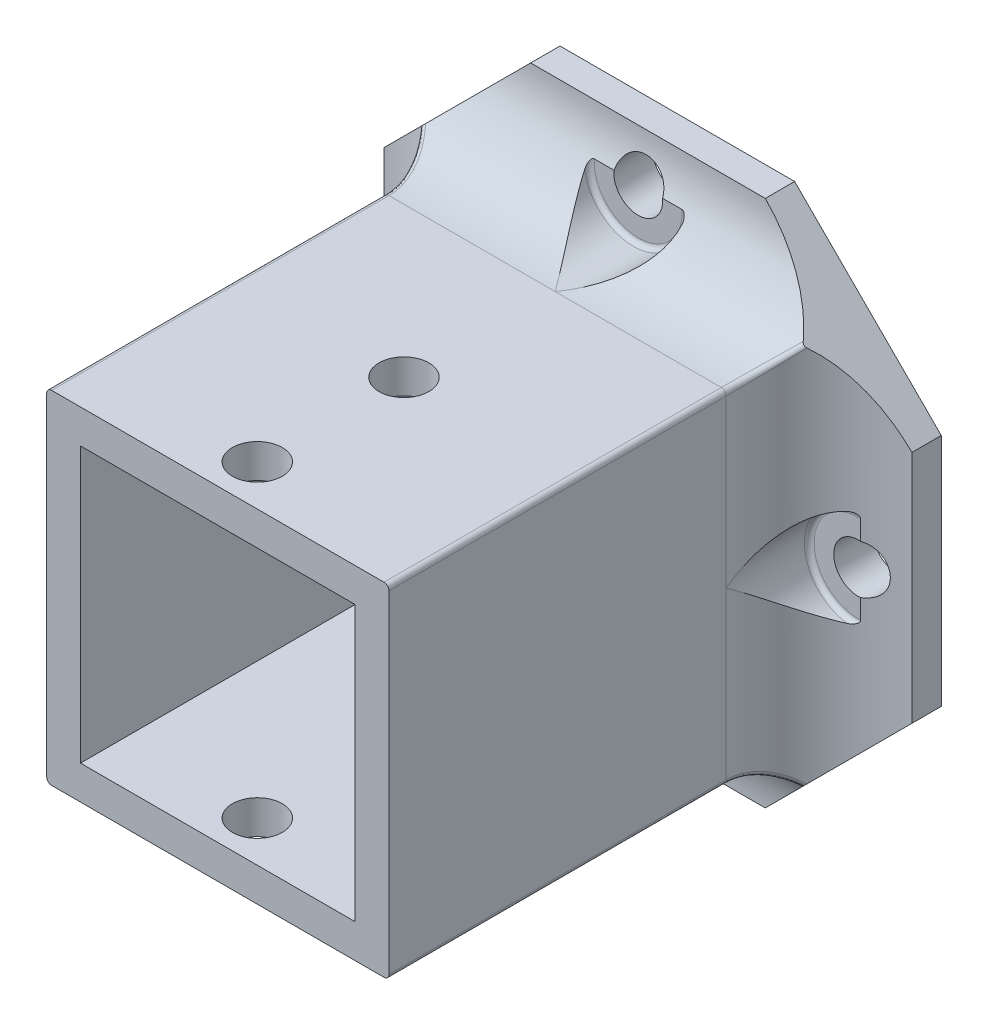
SolidWorks part; units mm, degrees
ref_plane "前视基准面" through (0, 0, 0) normal (0, 0, 1) x (1, 0, 0)
ref_plane "上视基准面" through (0, 0, 0) normal (0, 1, 0) x (1, 0, 0)
ref_plane "右视基准面" through (0, 0, 0) normal (1, 0, 0) x (0, 0, -1)
other "Configuration Table"
sketch "草图1" plane through (0, 0, 0) normal (0, 0, 1) x (1, 0, 0)
  line L1 (14.2, -14.2) -> (-14.2, -14.2)
  line L2 (14.2, -14.2) -> (14.2, 14.2)
  line L3 (14.2, 14.2) -> (-14.2, 14.2)
  line L4 (-14.2, -14.2) -> (-14.2, 14.2)
  line L5 (14.2, -14.2) -> (-14.2, 14.2) construction
  line L6 (14.2, 14.2) -> (-14.2, -14.2) construction
  point P0 (0, 0)
  dimension "D1" = 28.4
  dimension "D2" = 28.4
extrude "凸台-拉伸1" add sketch "草图1" along normal blind 3
sketch "草图2" plane through (0, 0, 3) normal (0, 0, 1) x (1, 0, 0)
  circle A0 centre (0, 0) radius 1
extrude "切除-拉伸1" cut sketch "草图2" against normal blind 3
sketch "草图5" plane through (0, 0, 0) normal (0, 0, -1) x (-1, 0, 0)
  circle A0 centre (0, 22.5) radius 2.5
  circle A1 centre (22.5, 0) radius 2.5
  circle A2 centre (-22.5, 0) radius 2.5
  circle A3 centre (0, -22.5) radius 2.5
sketch "草图6" plane through (0, 0, 3) normal (0, 0, 1) x (1, 0, 0)
  line L0 (12, 27) -> (27, 12)
  line L1 (27, -27) -> (-27, -27)
  line L2 (27, -27) -> (27, 27)
  line L3 (27, 27) -> (-27, 27)
  line L4 (-27, -27) -> (-27, 27)
  line L5 (27, -27) -> (-27, 27) construction
  line L6 (27, 27) -> (-27, -27) construction
  line L7 (27, -12) -> (12, -27)
  line L8 (-12, -27) -> (-27, -12)
  line L9 (-27, 12) -> (-12, 27)
  point P0 (0, 0)
  line M6 (-14.2, 14.2) -> (-14.2, -14.2)
  line M7 (-14.2, -14.2) -> (14.2, -14.2)
  line M8 (14.2, -14.2) -> (14.2, 14.2)
  line M9 (14.2, 14.2) -> (-14.2, 14.2)
  dimension "D1" = 4.5
  dimension "D2" = 15
  dimension "D3" = 15
  dimension "D4" = 15
  dimension "D5" = 15
  dimension "D6" = 15
  dimension "D7" = 15
  dimension "D8" = 15
  dimension "D9" = 15
extrude "凸台-拉伸3" add sketch "草图6" against normal blind 3 contours L9 L4 L8 L1 L7 L2 L0 L3 M6 M9 M8 M7 region at (18.96, 18.96, 3)
extrude "切除-拉伸2" cut sketch "草图5" against normal blind 3
sketch "草图7" plane through (0, 0, 3) normal (0, 0, 1) x (1, 0, 0)
  line L1 (17.5, -17.5) -> (-17.5, -17.5)
  line L3 (17.5, -17.5) -> (17.5, 17.5)
  line L4 (17.5, 17.5) -> (-17.5, 17.5)
  line L5 (-17.5, -17.5) -> (-17.5, 17.5)
  line L6 (17.5, -17.5) -> (-17.5, 17.5) construction
  line L15 (17.5, 17.5) -> (-17.5, -17.5) construction
  line L16 (14.05, -14.05) -> (-14.05, -14.05)
  line L21 (14.05, -14.05) -> (14.05, 14.05)
  line L22 (14.05, 14.05) -> (-14.05, 14.05)
  line L23 (-14.05, -14.05) -> (-14.05, 14.05)
  line L24 (14.05, -14.05) -> (-14.05, 14.05) construction
  line L25 (14.05, 14.05) -> (-14.05, -14.05) construction
  point P0 (0, 0)
  point P7 (0, 0)
  dimension "D1" = 28.1
  dimension "D2" = 28.1
  dimension "D3" = 35
  dimension "D4" = 35
extrude "凸台-拉伸4" add sketch "草图7" along normal blind 73 contours L5 L1 L3 L4 L16 L23 L22 L21 region at (0, -17.005, 3)
sketch "草图8" plane through (-17.5, 0, 0) normal (-1, 0, 0) x (0, 0, 1)
  line L0 (67, 17.5) -> (67, -17.5)
  line L4 (67, 17.5) -> (76, 17.5)
  line L5 (67, 17.5) -> (67, -17.5)
  line L6 (67, -17.5) -> (76, -17.5)
  line L7 (76, 17.5) -> (76, -17.5)
  dimension "D1" = 9
sketch "草图9" plane through (0, -17.5, 0) normal (0, -1, 0) x (1, 0, 0)
  line L2 (17.5, 76) -> (-17.5, 76) construction
  circle A0 centre (-0.1414, 42.82) radius 2.55
  circle A1 centre (-0.1414, 27.82) radius 2.55
  dimension "D1" = 15
  dimension "D2" = 33.18
extrude "切除-拉伸3" cut sketch "草图8" against normal blind 73 contours L0 region at (-17.5, 0, 71.5)
extrude "切除-拉伸4" cut sketch "草图9" against normal blind 73
fillet "圆角4" radius 9.5 4 edges at (0, -17.5, 3) (-17.5, 0, 3) (0, 17.5, 3) (17.5, 0, 3)
sketch "草图10" plane through (0, 0, 0) normal (0, 0, -1) x (-1, 0, 0)
  circle A0 centre (0, 22.5) radius 5
  circle A1 centre (22.5, 0) radius 5
  circle A2 centre (0, -22.5) radius 5
  circle A3 centre (-22.5, 0) radius 5
  point P12 (0, 0)
  dimension "D1" = 10
  dimension "D2" = 4
extrude "切除-拉伸6" cut sketch "草图10" against normal blind 10 from offset 4 offset against normal yes
fillet "圆角6" radius 0.5 12 edges at (17.5, 0, 4) (0, -17.5, 4) (-17.5, 0, 4) (0, 17.5, 4) (18.0139, 18.0139, 9.4178) (18.0139, -18.0139, 9.4178) (-18.0139, -18.0139, 9.4178) (-18.0139, 18.0139, 9.4178) (17.5, 17.5, 39.75) (17.5, -17.5, 39.75) (-17.5, -17.5, 39.75) (-17.5, 17.5, 39.75)
sketch "草图11" plane through (0, -17.5, 0) normal (0, -1, 0) x (1, 0, 0)
  line L0 (17.5, 67) -> (17.5, 12.5) construction
  line L1 (-17.5, 67) -> (17.5, 67)
  line L2 (-17.5, 67) -> (-17.5, 47)
  line L3 (-17.5, 47) -> (17.5, 47)
  line L4 (17.5, 67) -> (17.5, 47)
  dimension "D1" = 20
extrude "切除-拉伸7" cut sketch "草图11" against normal through all
